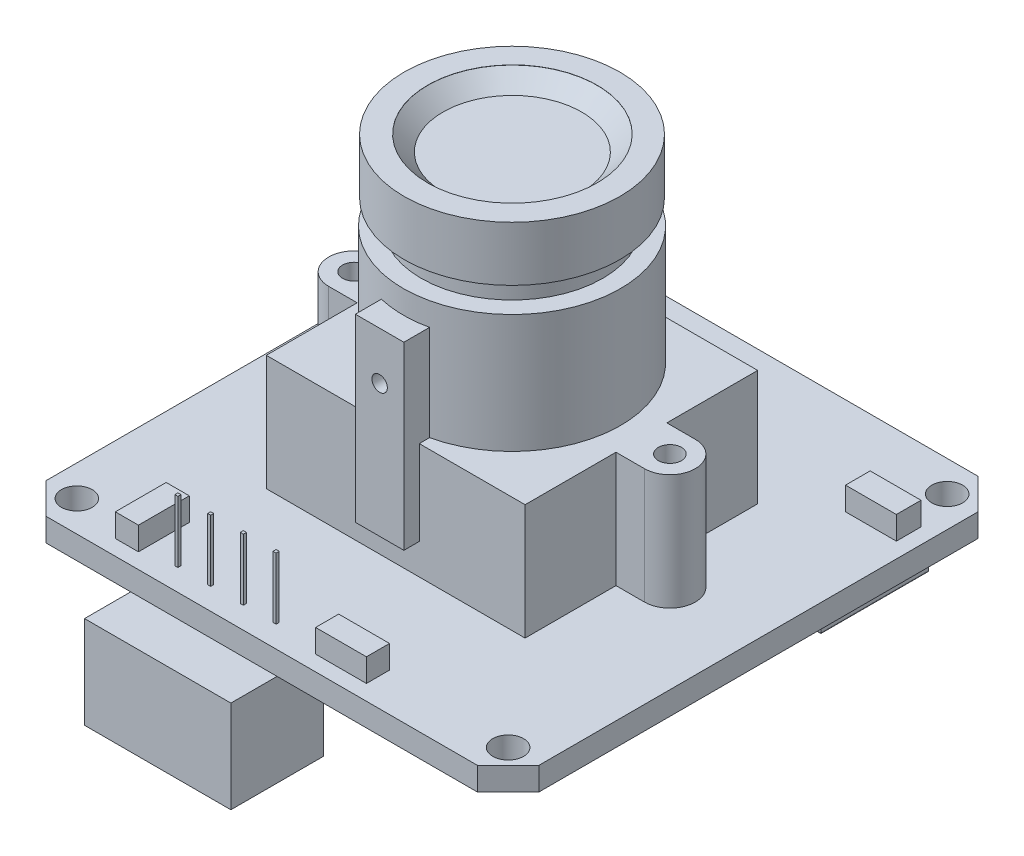
SolidWorks part; units mm, degrees
ref_plane "Front Plane" through (0, 0, 0) normal (0, 0, 1) x (1, 0, 0)
ref_plane "Top Plane" through (0, 0, 0) normal (0, 1, 0) x (1, 0, 0)
ref_plane "Right Plane" through (0, 0, 0) normal (1, 0, 0) x (0, 0, -1)
sketch "Sketch1" plane through (0, 0, 0) normal (0, 1, 0) x (1, 0, 0)
  line L0 (0, 2) -> (0, 30.5)
  line L1 (2, 32.5) -> (30, 32.5)
  line L2 (32, 30.5) -> (32, 2)
  line L3 (30, 0) -> (2, 0)
  line L20 (32, 2) -> (30, 0)
  line L21 (0, 2) -> (2, 0)
  line L22 (2, 32.5) -> (0, 30.5)
  line L23 (30, 32.5) -> (32, 30.5)
  circle A0 centre (2, 30.5) radius 1
  circle A1 centre (2, 2) radius 1
  circle A2 centre (30, 2) radius 1
  circle A3 centre (30, 30.5) radius 1
  dimension "D3" = 2.8284
  dimension "D1" = 2.8284
  dimension "D9" = 2
  dimension "D10" = 2
  dimension "D11" = 2
  dimension "D12" = 2
  dimension "D2" = 28.5
  dimension "D4" = 28
  dimension "D5" = 2.8284
  dimension "D6" = 28.5
  dimension "D7" = 2.8284
  dimension "D8" = 28
  dimension "D13" = 32.5
  dimension "D14" = 32.5
  dimension "D15" = 32
  dimension "D16" = 32
  dimension "D17" = 2
  dimension "D18" = 2
extrude "Boss-Extrude1" add sketch "Sketch1" along normal blind 1.5017
sketch "Sketch3" plane through (0, 1.5017, 0) normal (0, 1, 0) x (1, 0, 0)
  line L0 (24.4, 14.6) -> (24.4, 8.7)
  line L1 (7.6, 14.6) -> (7.6, 8.7)
  line L2 (5.75, 17.9) -> (7.6, 17.9)
  line L4 (5.75, 14.6) -> (7.6, 14.6)
  line L5 (24.4, 17.9) -> (26.25, 17.9)
  line L7 (26.25, 14.6) -> (24.4, 14.6)
  line L8 (7.6, 23.8) -> (7.6, 17.9)
  line L9 (7.6, 8.7) -> (16, 8.7)
  line L10 (7.6, 23.8) -> (16, 23.8)
  line L12 (24.4, 23.8) -> (16, 23.8)
  line L13 (24.4, 23.8) -> (24.4, 17.9)
  line L14 (24.4, 8.7) -> (16, 8.7)
  arc A0 (5.75, 17.9) -> (5.75, 14.6) centre (5.75, 16.25) ccw
  arc A1 (26.25, 14.6) -> (26.25, 17.9) centre (26.25, 16.25) ccw
  dimension "D8" = 1.65
  dimension "D10" = 1.65
  dimension "D1" = 16.8
  dimension "D2" = 8.4
  dimension "D3" = 8.4
  dimension "D4" = 5.9
  dimension "D5" = 5.9
  dimension "D6" = 15.1
  dimension "D7" = 3.3
  dimension "D9" = 3.3
  dimension "D11" = 5.9
  dimension "D12" = 5.9
  dimension "D13" = 15.1
  dimension "D14" = 16.8
  dimension "D15" = 8.4
  dimension "D16" = 8.4
  dimension "D17" = 1.85
  dimension "D18" = 1.85
  dimension "D19" = 1.85
  dimension "D20" = 1.85
extrude "Boss-Extrude3" add sketch "Sketch3" along normal blind 7.5
sketch "Sketch4" plane through (0, 9.0017, 0) normal (0, 1, 0) x (1, 0, 0)
  circle A0 centre (16, 16.25) radius 7.05
  dimension "D1" = 14.1
extrude "Boss-Extrude4" add sketch "Sketch4" along normal blind 7.7
sketch "Sketch6" plane through (0, 16.7017, 0) normal (0, 1, 0) x (1, 0, 0)
  circle A2 centre (16, 16.25) radius 5.9
  dimension "D1" = 11.8
extrude "Boss-Extrude5" add sketch "Sketch6" along normal blind 1.6
sketch "Sketch7" plane through (0, 18.3017, 0) normal (0, 1, 0) x (1, 0, 0)
  circle A2 centre (16, 16.25) radius 7
  circle M1 centre (16, 16.25) radius 5.9
  dimension "D1" = 14
extrude "Boss-Extrude6" add sketch "Sketch7" along normal blind 3.55 contours A2 M1 | M1 | M1 region at (9.198, 18.3017, -16.25) region at (16, 18.3017, -16.25)
sketch "Sketch9" plane through (0, 21.8517, 0) normal (0, 1, 0) x (1, 0, 0)
  circle A2 centre (16, 16.275) radius 5.5
extrude "Cut-Extrude1" cut sketch "Sketch9" against normal blind 0.01
sketch "Sketch10" plane through (0, 21.8417, 0) normal (0, 1, 0) x (1, 0, 0)
  circle A1 centre (16, 16.275) radius 4.5
  dimension "D1" = 9
extrude "Cut-Extrude2" cut sketch "Sketch10" against normal blind 1 contours A1
chamfer "Chamfer3" distance 1 angle 45 1 edges at (16, 21.8417, -11.775)
sketch "Sketch11" plane through (0, 9.0017, 0) normal (0, 1, 0) x (1, 0, 0)
  circle A0 centre (5.75, 16.25) radius 0.75
  circle A1 centre (26.25, 16.25) radius 0.75
  dimension "D1" = 1.5
  dimension "D2" = 1.5
extrude "Cut-Extrude3" cut sketch "Sketch11" against normal blind 9
sketch "Sketch13" plane through (0, 0, -8.7) normal (0, 0, 1) x (1, 0, 0)
  line L0 (14.3814, 9.0017) -> (14.3814, 15.2017)
  line L1 (7.6, 9.0017) -> (24.4, 9.0017) construction
  line L2 (14.3814, 15.2017) -> (17.5314, 15.2017)
  line L3 (17.5314, 15.2017) -> (17.5314, 9.0017)
  line L5 (17.5314, 3.5017) -> (14.3814, 3.5017)
  line L6 (14.3814, 3.5017) -> (14.3814, 9.0017)
  line L8 (17.5314, 9.0017) -> (17.5314, 3.5017)
  circle A0 centre (15.9564, 12.1) radius 0.5
  dimension "D1" = 6.2
  dimension "D4" = 1
  dimension "D2" = 5.5
  dimension "D3" = 11.7
  dimension "D5" = 3.15
extrude "Boss-Extrude8" add sketch "Sketch13" along normal blind 1 and the other way blind 1
sketch "Sketch14" plane through (0, 0, 0) normal (0, -1, 0) x (1, 0, 0)
  line L0 (7.5, 3) -> (8, 3)
  line L1 (7.5, -3) -> (8, -3)
  line L2 (8, -2.5) -> (8, 2.5)
  line L3 (17, -3) -> (16.5, -3)
  line L4 (7.5, -3) -> (7.5, 3)
  line L5 (7.5, 3) -> (17, 3)
  line L6 (17, 3) -> (17, -3)
  line L7 (7.5, -3) -> (17, -3)
  line L8 (16.5, -2.5) -> (16.5, 2.5)
  line L9 (16.5, 3) -> (17, 3)
  line L10 (7.5, 3) -> (7.5, 2.5)
  line L12 (8, 2.5) -> (16.5, 2.5)
  line L14 (7.5, -3) -> (7.5, -2.5)
  line L16 (8, -2.5) -> (10.5, -2.5)
  line L18 (8, -2.5) -> (10.5, -2.5)
  line L19 (10.5, -2.5) -> (10.5, -3)
  line L20 (10.5, -3) -> (7.5, -3)
  line L21 (16.5, -2.5) -> (14, -2.5)
  line L22 (14, -2.5) -> (14, -3)
  line L23 (14, -3) -> (17, -3)
  line L24 (14, -2.5) -> (16.5, -2.5)
  line M8 (30, 0) -> (2, 0)
  dimension "D1" = 9.5
  dimension "D2" = 8.5
  dimension "D3" = 6
  dimension "D4" = 5
  dimension "D5" = 3
  dimension "D6" = 2.5
  dimension "D7" = 0.5
  dimension "D8" = 0.5
  dimension "D9" = 0.5
  dimension "D10" = 0.5
extrude "Boss-Extrude9" add sketch "Sketch14" along normal blind 2 contours L12 L2 L8 M8 | L22 L21 L8 L2 L16 L19 L7 M8 region at (12.25, 0, -1.3641) region at (12.25, 0, 1.25)
extrude "Boss-Extrude10" add sketch "Sketch14<4>" along normal blind 6 contours L2 L12 L8 L6 L5 L0 L4 M8 | L21 L22 L7 L3 L6 L8 M8 | L19 L16 L2 L4 L1 L7 M8 region at (7.75, 0, 2.9004) region at (7.75, 0, -0.0424) region at (16.9576, 0, -1.5)
sketch "Sketch14<4>" plane through (0, 0, 0) normal (0, -1, 0) x (1, 0, 0) same geometry as "Sketch14"
sketch "Sketch16" plane through (0, 0, 0) normal (0, -1, 0) x (1, 0, 0)
  line L0 (27, -2) -> (18, -2)
  line L1 (17.5, -2.5) -> (17.5, -11.5)
  line L2 (18, -12) -> (27, -12)
  line L3 (27.5, -11.5) -> (27.5, -2.5)
  line L14 (27.5, -2.5) -> (27, -2)
  line L15 (17.5, -2.5) -> (18, -2)
  line L17 (17.5, -11.5) -> (18, -12)
  line L18 (27, -12) -> (27.5, -11.5)
  dimension "D1" = 9
  dimension "D2" = 10
  dimension "D3" = 9
  dimension "D4" = 10
  dimension "D5" = 0.7071
  dimension "D6" = 0.7071
  dimension "D7" = 9
  dimension "D8" = 10
  dimension "D9" = 10
  dimension "D10" = 9
  dimension "D11" = 0.7071
  dimension "D12" = 0.7071
extrude "Boss-Extrude12" add sketch "Sketch16" along normal blind 1.5
sketch "Sketch17" plane through (0, 0, 0) normal (0, -1, 0) x (-1, 0, 0)
  line L3 (-31, 21.3) -> (-26.5, 21.3)
  line L4 (-26.5, 21.3) -> (-26.5, 28.3)
  line L5 (-26.5, 28.3) -> (-31, 28.3)
  line L6 (-31, 28.3) -> (-31, 21.3)
  dimension "D1" = 4.5
  dimension "D2" = 7
extrude "Boss-Extrude13" add sketch "Sketch17" along normal blind 1.3
sketch "Sketch18" plane through (0, 0, 0) normal (0, -1, 0) x (1, 0, 0)
  line L1 (25.5, -21.3) -> (25.5, -29.6)
  line L2 (25.5, -29.6) -> (7.4, -29.6)
  line L3 (7.4, -29.6) -> (7.4, -21.3)
  line L4 (7.4, -21.3) -> (25.5, -21.3)
  dimension "D1" = 18.1
  dimension "D2" = 8.3
extrude "Boss-Extrude14" add sketch "Sketch18" along normal blind 2.5
sketch "Sketch19" plane through (0, 0, 0) normal (0, -1, 0) x (1, 0, 0)
  circle A1 centre (5.75, -16.25) radius 2
  circle A3 centre (26.25, -16.25) radius 2
extrude "Cut-Extrude4" cut sketch "Sketch19" against normal blind 0.01
fillet "Fillet2" radius 0.1 4 edges at (31, -1.3, -24.8) (28.75, -1.3, -28.3) (26.5, -1.3, -24.8) (28.75, -1.3, -21.3)
sketch "Sketch20" plane through (0, 0, 0) normal (0, -1, 0) x (-1, 0, 0)
  line L0 (-2, 18.2) -> (-2, 15.2)
  line L1 (-2, 15.2) -> (-3.6, 15.2)
  line L2 (-3.6, 15.2) -> (-3.6, 18.2)
  line L3 (-3.6, 18.2) -> (-2, 18.2)
  line L4 (-2, 18.2) -> (-2, 15.2)
  dimension "D1" = 3
  dimension "D2" = 1.6
extrude "Boss-Extrude16" add sketch "Sketch20" along normal blind 1.5 contours L3 L2 L1 L0 region at (2.8, 0, -16.7)
sketch "Sketch21" plane through (0, 0, 0) normal (0, -1, 0) x (-1, 0, 0)
  line L0 (-0.15, 21.7) -> (-3.15, 21.7)
  line L4 (-0.15, 21.7) -> (-0.15, 23.2)
  line L5 (-0.15, 23.2) -> (-3.15, 23.2)
  line L6 (-3.15, 23.2) -> (-3.15, 21.7)
extrude "Boss-Extrude17" add sketch "Sketch21" along normal blind 1.5
sketch "Sketch22" plane through (0, 0, 0) normal (0, -1, 0) x (1, 0, 0)
  line L2 (1.65, -25.6474) -> (3.15, -25.6474)
  line L3 (3.15, -25.6474) -> (4.65, -25.6474)
  line L4 (4.65, -25.6474) -> (4.65, -27.1474)
  line L5 (1.65, -25.6474) -> (1.65, -27.1474)
  line L6 (1.65, -27.1474) -> (4.65, -27.1474)
  dimension "D1" = 1.5
  dimension "D2" = 3
extrude "Boss-Extrude18" add sketch "Sketch22" along normal blind 1.5
sketch "Sketch23" plane through (0, 0, 0) normal (0, -1, 0) x (1, 0, 0)
  line L0 (12.35, -5.9894) -> (10.7, -5.9894)
  line L1 (14, -5.9894) -> (14, -14.6894)
  line L2 (14, -14.6894) -> (10.7, -14.6894)
  line L3 (10.7, -14.6894) -> (10.7, -5.9894)
  line L4 (10.7, -5.9894) -> (14, -5.9894)
  line L5 (12.35, -5.9894) -> (14, -5.9894)
  line L6 (10.7, -5.9894) -> (10.7, -6.9894)
  line L8 (14, -6.9894) -> (14, -5.9894)
  line L10 (12.35, -5.9894) -> (14, -5.9894)
  circle A0 centre (11.525, -6.4894) radius 0.25
  circle A1 centre (13.2572, -6.4894) radius 0.25
extrude "Boss-Extrude19" add sketch "Sketch23" along normal blind 1.65 contours A0 | A1 region at (11.525, 0, -6.4894) region at (13.2572, 0, -6.4894)
sketch "Sketch24" plane through (0, -1.65, 0) normal (0, -1, 0) x (1, 0, 0)
  line L5 (12.3911, -5.9394) -> (12.3911, -14.9394)
sketch3d "3DSketch2"
  circle A0 centre (12.3911, -1.65, -14.9394) radius 1.65
  point P3 (12.3911, -1.65, -13.2894)
sketch "Sketch25" plane through (0, 1.5017, 0) normal (0, 1, 0) x (1, 0, 0)
  line L0 (0, 2) -> (0, 0)
  line L1 (0, 0) -> (17, 0)
  line L2 (7.5, 0) -> (17, 0)
  line L3 (17, 0) -> (16.5, 0)
  line L4 (16.5, 2.5) -> (16.5, -2.5) construction
  line L7 (9.0625, 1.6) -> (8.9625, 1.6)
  line L8 (8.9625, 1.6) -> (8.9625, 1.4)
  line L9 (8.9625, 1.4) -> (9.1625, 1.4)
  line L10 (9.1625, 1.4) -> (9.1625, 1.6)
  line L11 (9.1625, 1.6) -> (9.0625, 1.6)
  line L13 (11.1875, 1.6) -> (11.0875, 1.6)
  line L15 (11.0875, 1.6) -> (11.0875, 1.4)
  line L16 (11.0875, 1.4) -> (11.2875, 1.4)
  line L17 (11.2875, 1.4) -> (11.2875, 1.6)
  line L18 (11.2875, 1.6) -> (11.1875, 1.6)
  line L21 (8, 2.5) -> (8, -2.5) construction
  line L22 (13.3125, 1.6) -> (13.2125, 1.6)
  line L23 (13.2125, 1.6) -> (13.2125, 1.4)
  line L24 (13.2125, 1.4) -> (13.4125, 1.4)
  line L25 (13.4125, 1.4) -> (13.4125, 1.6)
  line L26 (13.4125, 1.6) -> (13.3125, 1.6)
  line L28 (15.4375, 1.6) -> (15.3375, 1.6)
  line L29 (8, 0) -> (16.5, 0)
  line L30 (15.3375, 1.6) -> (15.3375, 1.4)
  line L31 (15.3375, 1.4) -> (15.5375, 1.4)
  line L32 (15.5375, 1.4) -> (15.5375, 1.6)
  line L33 (15.5375, 1.6) -> (15.4375, 1.6)
sketch "Sketch26" plane through (0, 1.5017, 0) normal (0, 1, 0) x (1, 0, 0)
  line L3 (31, 26.2) -> (31, 27.8)
  line L4 (31, 27.8) -> (27.7, 27.8)
  line L5 (27.7, 27.8) -> (27.7, 26.2)
  line L6 (27.7, 26.2) -> (31, 26.2)
  line L7 (31, 27.8) -> (31, 26.2)
  dimension "D1" = 3.3
  dimension "D2" = 1.6
extrude "Boss-Extrude21" add sketch "Sketch26" along normal blind 1.5 contours L5 L6 L3 L4 region at (29.35, 1.5017, -27)
sketch "Sketch27" plane through (0, 1.5017, 0) normal (0, 1, 0) x (1, 0, 0)
  line L4 (1, 19) -> (4.3, 19)
  line L5 (4.3, 19) -> (4.3, 20.5)
  line L6 (4.3, 20.5) -> (1, 20.5)
  line L7 (1, 20.5) -> (1, 19)
  line L8 (1, 20.5) -> (1, 19)
  dimension "D1" = 1.5
  dimension "D2" = 3.3
extrude "Boss-Extrude22" add sketch "Sketch27" along normal blind 1.5 contours L6 L7 L4 L5 region at (2.65, 1.5017, -19.75)
sketch "Sketch28" plane through (0, 1.5017, 0) normal (0, 1, 0) x (1, 0, 0)
  line L4 (5.5, 1) -> (7, 1)
  line L5 (7, 1) -> (7, 4.3)
  line L6 (7, 4.3) -> (5.5, 4.3)
  line L7 (5.5, 4.3) -> (5.5, 1)
  line L8 (5.5, 1) -> (7, 1)
  dimension "D1" = 1.5
  dimension "D2" = 3.3
extrude "Boss-Extrude23" add sketch "Sketch28" along normal blind 1.5 contours L6 L7 L4 L5 region at (6.25, 1.5017, -2.65)
sketch "Sketch29" plane through (0, 1.5017, 0) normal (0, 1, 0) x (1, 0, 0)
  line L3 (18.5, 1) -> (18.5, 2.5)
  line L4 (18.5, 2.5) -> (21.8, 2.5)
  line L5 (21.8, 2.5) -> (21.8, 1)
  line L6 (21.8, 1) -> (18.5, 1)
  dimension "D1" = 1.5
  dimension "D2" = 3.3
extrude "Boss-Extrude24" add sketch "Sketch29" along normal blind 1.5
extrude "Boss-Extrude25" add sketch "Sketch25" along normal blind 4 and the other way blind 5.5 contours L10 L11 L7 L8 L9 | L17 L18 L13 L15 L16 | L25 L26 L22 L23 L24 | L32 L33 L28 L30 L31 region at (9.0625, 1.5017, -1.5) region at (11.1875, 1.5017, -1.5) region at (13.3125, 1.5017, -1.5)
scale "Scale1" scale about centroid uniform scaling yes scale factor 8
